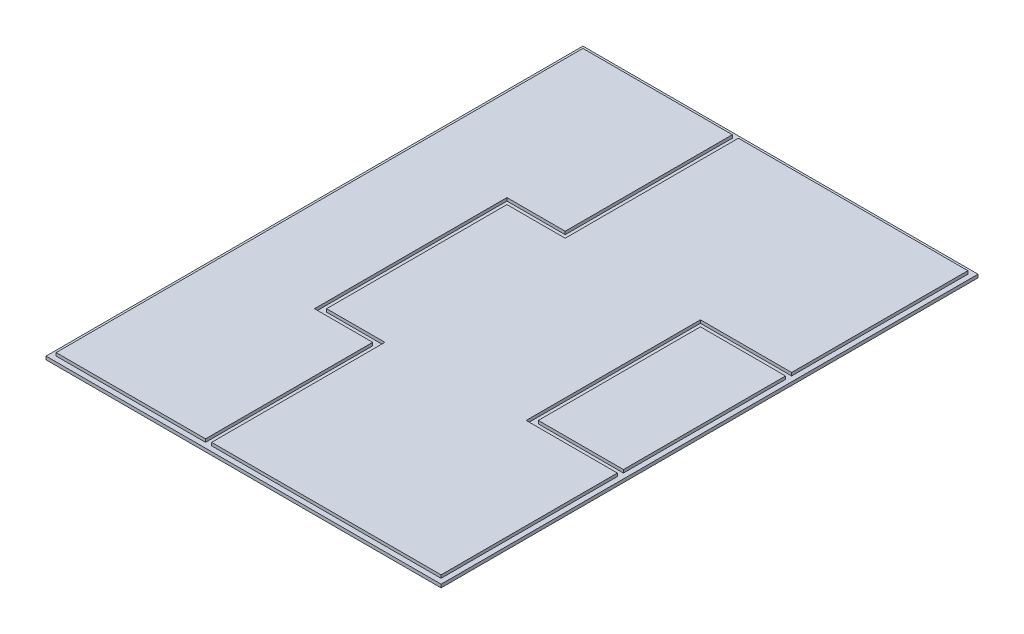
SolidWorks part; units mm, degrees
ref_plane "Front Plane" through (0, 0, 0) normal (0, 0, 1) x (1, 0, 0)
ref_plane "Top Plane" through (0, 0, 0) normal (0, 1, 0) x (1, 0, 0)
ref_plane "Right Plane" through (0, 0, 0) normal (1, 0, 0) x (0, 0, -1)
sketch "Sketch1" plane through (0, 0, 0) normal (0, 1, 0) x (1, 0, 0)
  line L1 (-13.7445, 33.5859) -> (25.2555, 33.5859)
  line L2 (-13.7445, 33.5859) -> (-13.7445, -19.4141)
  line L3 (-13.7445, -19.4141) -> (25.2555, -19.4141)
  line L4 (25.2555, 33.5859) -> (25.2555, -19.4141)
  dimension "D1" = 39
  dimension "D2" = 53
extrude "Boss-Extrude1" add sketch "Sketch1" along normal blind 0.32
sketch "Sketch2" plane through (0, 0.32, 0) normal (0, 1, 0) x (1, 0, 0)
  line L0 (-13.2445, 33.0859) -> (-13.2445, -18.9141)
  line L1 (-13.2445, -18.9141) -> (1.5055, -18.9141)
  line L2 (1.5055, -18.9141) -> (1.5055, -2.4141)
  line L3 (1.5055, -2.4141) -> (-4.2445, -2.4141)
  line L4 (-4.2445, -2.4141) -> (-4.2445, 16.5859)
  line L5 (-4.2445, 16.5859) -> (1.5055, 16.5859)
  line L6 (1.5055, 16.5859) -> (1.5055, 33.0859)
  line L7 (1.5055, 33.0859) -> (-13.2445, 33.0859)
  line L8 (25.2555, 33.5859) -> (-13.7445, 33.5859) construction
  line L9 (-13.7445, -19.4141) -> (25.2555, -19.4141) construction
  line L10 (-13.7445, 33.5859) -> (-13.7445, -19.4141) construction
  line L11 (2.1055, 33.0859) -> (24.7555, 33.0859)
  line L12 (24.7555, 33.0859) -> (24.7555, 15.6859)
  line L13 (24.7555, 15.6859) -> (15.7555, 15.6859)
  line L14 (15.7555, 15.6859) -> (15.7555, -1.5141)
  line L15 (15.7555, -1.5141) -> (24.7555, -1.5141)
  line L16 (24.7555, -1.5141) -> (24.7555, -18.9141)
  line L17 (24.7555, -18.9141) -> (2.1055, -18.9141)
  line L18 (2.1055, -18.9141) -> (2.1055, -1.8141)
  line L19 (2.1055, -1.8141) -> (-3.6445, -1.8141)
  line L20 (-3.6445, -1.8141) -> (-3.6445, 15.9859)
  line L21 (-3.6445, 15.9859) -> (2.1055, 15.9859)
  line L22 (2.1055, 15.9859) -> (2.1055, 33.0859)
  line L23 (25.2555, -19.4141) -> (25.2555, 33.5859) construction
  line L25 (16.3555, 15.0859) -> (24.7555, 15.0859)
  line L26 (16.3555, 15.0859) -> (16.3555, -0.9141)
  line L27 (16.3555, -0.9141) -> (24.7555, -0.9141)
  line L28 (24.7555, 15.0859) -> (24.7555, -0.9141)
  dimension "D1" = 0.5
  dimension "D2" = 0.5
  dimension "D3" = 0.5
  dimension "D4" = 14.75
  dimension "D5" = 14.75
  dimension "D6" = 9
  dimension "D7" = 19
  dimension "D8" = 16.5
  dimension "D9" = 0.6
  dimension "D10" = 0.6
  dimension "D11" = 0.6
  dimension "D12" = 0.6
  dimension "D13" = 0.6
  dimension "D14" = 0.5
  dimension "D15" = 0.5
  dimension "D16" = 0.5
  dimension "D17" = 0.5
  dimension "D18" = 17.2
  dimension "D19" = 17.4
  dimension "D20" = 17.4
  dimension "D21" = 9
  dimension "D22" = 0.5
  dimension "D23" = 0.6
  dimension "D24" = 0.6
  dimension "D25" = 0.6
extrude "Boss-Extrude2" add sketch "Sketch2" along normal blind 0.3
split "Split1" bodies to split 102 resulting bodies 103 104 105 106 split by face at (5.7555, 0.32, -7.0859)
sketch "Sketch5" plane through (0, 0, 0) normal (0, -1, 0) x (1, 0, 0)
  line L0 (-13.7445, -33.5859) -> (-13.7445, 19.4141) construction
  line L1 (-13.2445, 18.9141) -> (24.7555, 18.9141)
  line L2 (-13.2445, 18.9141) -> (-13.2445, -33.0859)
  line L3 (-13.2445, -33.0859) -> (24.7555, -33.0859)
  line L4 (24.7555, 18.9141) -> (24.7555, -33.0859)
  line L5 (-13.7445, 19.4141) -> (25.2555, 19.4141) construction
  line L6 (25.2555, 19.4141) -> (25.2555, -33.5859) construction
  line L7 (25.2555, -33.5859) -> (-13.7445, -33.5859) construction
  dimension "D1" = 0.5
  dimension "D2" = 0.5
  dimension "D3" = 0.5
  dimension "D4" = 0.5
extrude "Boss-Extrude3" add sketch "Sketch5" along normal blind 0.3
split "Split2" bodies to split 107 resulting bodies 108 109 split by face at (5.7555, 0, -7.0859)
